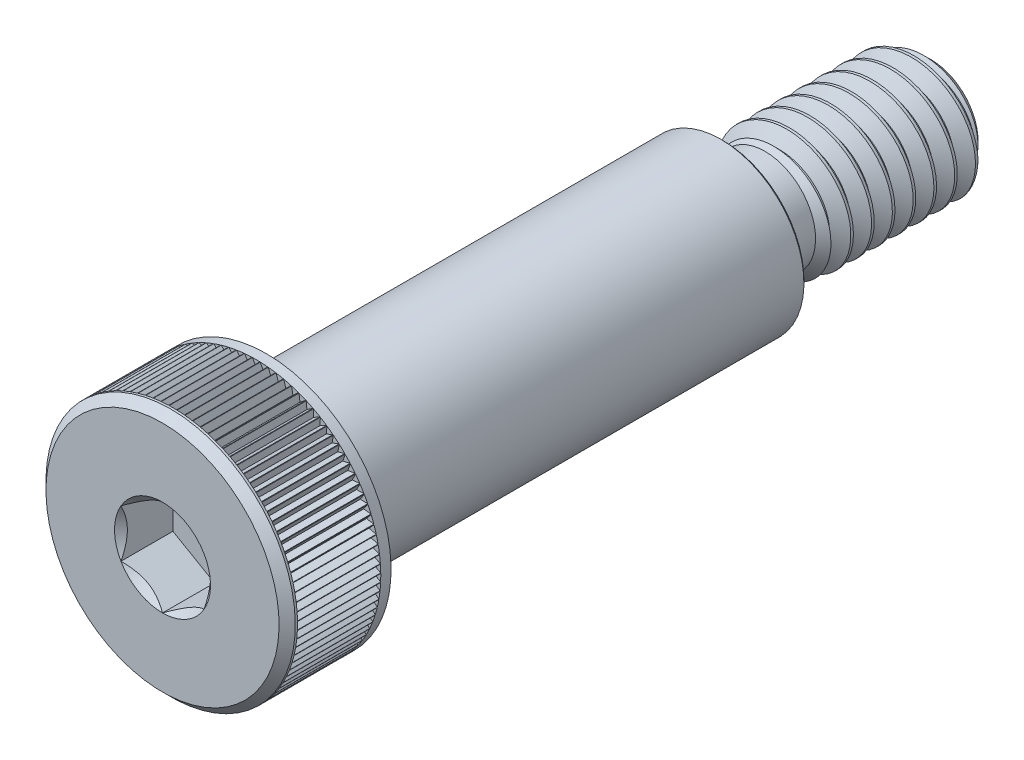
SolidWorks part; units mm, degrees
ref_plane "Front" through (0, 0, 0) normal (0, 0, 1) x (1, 0, 0)
ref_plane "Top" through (0, 0, 0) normal (0, 1, 0) x (1, 0, 0)
ref_plane "Right" through (0, 0, 0) normal (1, 0, 0) x (0, 0, -1)
sketch "Sketch1" plane through (0, 0, 0) normal (1, 0, 0) x (0, 0, -1)
  line L0 (0, 9.525) -> (7.9375, 9.525)
  line L1 (7.9375, 9.525) -> (7.9375, 6.35)
  line L2 (7.9375, 6.35) -> (42.8625, 6.35)
  line L3 (42.8625, 6.35) -> (42.8625, 4.7625)
  line L4 (42.8625, 4.7625) -> (58.7375, 4.7625)
  line L5 (58.7375, 4.7625) -> (58.7375, 0)
  line L6 (58.7375, 0) -> (0, 0)
  line L7 (0, 0) -> (0, 9.525)
  line L8 (0, 9.525) -> (0, -9.525) construction
  line L9 (58.7375, 4.7625) -> (58.7375, -4.7625) construction
  line L10 (42.8625, 6.35) -> (42.8625, -6.35) construction
  line L11 (58.7375, -4.7625) -> (57.0597, -4.7625) construction
  line L12 (25.4, 0) -> (25.4, 6.35) construction
  point P8 (56.3562, -4.7625)
  point P12 (42.8625, 0)
  point P17 (11.43, 6.35)
  point P18 (25.4, 0)
  point P19 (25.4, 6.35)
  point P20 (39.37, 6.35)
  point P21 (39.37, -6.35)
  point P22 (11.43, -6.35)
  dimension "D3" = 17.4625
  dimension "Head Dia" = 19.05
  dimension "Head Ht" = 7.9375
  dimension "Thread Lg" = 15.875
  dimension "Thread Dia" = 9.525
  dimension "Shoulder Dia" = 12.7
  dimension "Shoulder Lg" = 34.925
  dimension "D1" = 2.3813
  dimension "D2" = 1.6778
  dimension "D4" = 3.4925
revolve "Revolve1" add sketch "Sketch1" angle 360 mid plane about L6
ref_plane "Plane1" through (0, 0, -58.7375) normal (0, 0, 1) x (1, 0, 0)
sketch "Sketch3" plane through (0, 0, -58.7375) normal (0, 0, 1) x (1, 0, 0)
  circle A0 centre (0, 0) radius 4.7625
sketch "Sketch5" plane through (0, 0, 0) normal (1, 0, 0) x (0, 0, -1)
  line L0 (42.8625, 6.35) -> (48.5267, 6.35)
  line L1 (48.5267, 6.35) -> (46.0375, 3.8608)
  line L2 (46.0375, 3.8608) -> (43.7642, 3.8608)
  line L3 (42.8625, 6.35) -> (42.8625, 4.7625)
  line L5 (42.8625, 4.7625) -> (58.7375, 4.7625) construction
  line L6 (58.7375, 0) -> (46.0375, 0) construction
  line L7 (52.3875, 0) -> (52.3875, -4.7625) construction
  arc A0 (42.8625, 4.7625) -> (43.7642, 3.8608) centre (43.7642, 4.7625) ccw
  dimension "D1" = 45
  dimension "CADB" = 3.175
  dimension "CADA" = 7.7216
revolve "Cut-Revolve1" cut sketch "Sketch5" angle 360 mid plane about L6
chamfer "Chamfer1" distance 1.1906 angle 45 1 edges at (0, 4.7625, -58.7375)
chamfer "Chamfer2" distance 0.6191 angle 45 1 edges at (0, 9.525, 0)
chamfer "Chamfer3" distance 0.2032 angle 45 1 edges at (0, 6.35, -42.8625)
sketch "Sketch10" plane through (0, 0, 0) normal (1, 0, 0) x (0, 0, -1)
  line L0 (0.6191, 0) -> (7.3184, 0) construction
  line L1 (0.6191, -9.525) -> (0.6191, 9.525) construction
  line L3 (0.6191, 0) -> (0, 0) construction
  line L4 (7.3184, 0) -> (7.9375, 0) construction
  line L5 (7.9375, -9.525) -> (7.9375, 9.525) construction
  point P6 (3.9687, 0)
  dimension "D1" = 6.6992
ref_plane "Plane2" through (0, 0, -3.9687) normal (0, 0, 1) x (1, 0, 0)
sketch "Sketch11" plane through (0, 0, -3.9687) normal (0, 0, 1) x (1, 0, 0)
  line L0 (0, 9.0297) -> (0, 9.525) construction
  line L1 (0, 9.0297) -> (0.286, 9.525)
  line L2 (0, 9.0297) -> (-0.286, 9.525)
  line L3 (-0.286, 9.525) -> (0.286, 9.525)
  line L4 (0, 0) -> (-0.286, 9.525) construction
  line L5 (0.286, 9.525) -> (0, 0) construction
  circle A1 centre (0, 0) radius 9.525 construction
  circle A2 centre (0, 0) radius 9.0297 construction
  circle A3 centre (0, 0) radius 8.9059 construction
  point P3 (0, 0.0018)
  point P8 (2.3908, 0.7309)
  dimension "D1" = 0.4953
  dimension "D2" = 3.439
extrude "Cut-Extrude5" cut sketch "Sketch11" against normal mid plane 6.3643
pattern_circular "CirPattern1" count 99 over 360 about axis through (0, 0, -58.7375) along (0, 0, -1) of "Cut-Extrude5"
sketch "Sketch8" plane through (0, 0, 0) normal (0, 0, 1) x (1, 0, 0)
  line L1 (3.175, 1.8331) -> (0, 3.6662)
  line L2 (0, 3.6662) -> (-3.175, 1.8331)
  line L3 (-3.175, 1.8331) -> (-3.175, -1.8331)
  line L4 (-3.175, -1.8331) -> (0, -3.6662)
  line L5 (0, -3.6662) -> (3.175, -1.8331)
  line L6 (3.175, -1.8331) -> (3.175, 1.8331)
  circle A0 centre (0, 0) radius 3.175 construction
  dimension "Hex" = 6.35
extrude "Cut-Extrude2" cut sketch "Sketch8" against normal blind 3.9688
sketch "Sketch9" plane through (0, 0, 0) normal (0, 0, 1) x (1, 0, 0)
  circle A0 centre (0, 0) radius 3.6662
extrude "Cut-Extrude4" cut sketch "Sketch9" against normal blind 3.9688 draft 45
sketch "Front Sketch" plane through (0, 0, 0) normal (0, 0, 1) x (1, 0, 0)
  line L0 (3.175, -1.8331) -> (3.175, 1.8331) construction
  line L1 (-3.175, 1.8331) -> (-3.175, -1.8331) construction
  circle A0 centre (0, 0) radius 9.525 construction
  point P4 (-3.175, 0)
  point P5 (3.175, 0)
  point P6 (9.525, 0)
  point P9 (-9.525, 0)
ref_plane "Contact Plane 1" through (0, 0, -7.9375) normal (0, 0, -1) x (-1, 0, 0)
ref_axis "Center Axis 1" through (0, 0, -58.7375) along (0, 0, 1)
curve "Helix/Spiral1" pitch 1.5875 height 17.4625 radius 4.7625 centre (0, 0, -58.7375) axis (0, 0, 1) start towards (0, 1, 0)
sketch "Sketch4" plane through (0, 0, 0) normal (1, 0, 0) x (0, 0, -1)
  line L0 (58.6383, 4.9344) -> (60.2258, 4.9344) construction
  line L1 (60.2258, 4.9344) -> (59.432, 3.5595) construction
  line L3 (59.432, 3.5595) -> (58.6383, 4.9344) construction
  line L4 (58.6879, 4.8484) -> (60.1762, 4.8484) construction
  line L5 (58.7375, 4.7625) -> (60.1266, 4.7625) construction
  line L6 (59.3328, 3.7314) -> (59.5312, 3.7314) construction
  line L7 (59.432, 3.7314) -> (59.432, 3.5595) construction
  line L8 (59.432, 4.9344) -> (59.432, 4.7625) construction
  line L9 (58.6879, 4.8484) -> (60.1762, 4.8484)
  line L10 (60.1762, 4.8484) -> (59.5312, 3.7314)
  line L11 (59.5312, 3.7314) -> (59.3328, 3.7314)
  line L12 (59.3328, 3.7314) -> (58.6879, 4.8484)
  point P14 (59.432, 4.8484)
  point P15 (59.432, 4.9344)
  dimension "D1" = 1.5875
  dimension "D2" = 0.1984
sweep "Cut-Sweep1" cut profiles "Sketch4" path "Helix/Spiral1" align with end faces yes
sketch "Sketch12" plane through (0, 0, 0) normal (1, 0, 0) x (0, 0, -1)
  line L1 (42.8625, 6.1468) -> (42.6593, 6.35)
  line L2 (42.6593, 6.35) -> (7.9375, 6.35)
  line L3 (7.9375, 6.35) -> (7.9375, 0)
  line L4 (7.9375, -9.525) -> (7.9375, 9.525) construction
  line L5 (7.9375, 0) -> (42.8625, 0)
  line L6 (42.8625, 6.1468) -> (42.8625, 4.7625)
  line L7 (46.0375, 3.8608) -> (43.7642, 3.8608) construction
  line L8 (46.0375, 3.8608) -> (43.7642, 3.8608)
  line L9 (46.0375, 3.8608) -> (46.0375, 0)
  line L10 (46.0375, 0) -> (42.8625, 0)
  arc A0 (42.8625, 4.7625) -> (43.7642, 3.8608) centre (43.7642, 4.7625) ccw construction
  arc A1 (42.8625, 4.7625) -> (43.7642, 3.8608) centre (43.7642, 4.7625) ccw
revolve "Revolve2" add sketch "Sketch12" angle 360 about L5
equation "\"D3@Helix/Spiral1\" = \"Thread Lg@Sketch1\" + \"D4@Helix/Spiral1\""
equation "\"D1@Chamfer1\" = \"Thread Dia@Sketch1\" * .125"
equation "\"D1@Cut-Extrude2\"= \"Head Ht@Sketch1\" * .5"
equation "\"D1@Cut-Extrude4\" = \"D1@Cut-Extrude2\""
equation "\"D1@Chamfer2\" = \"Head Dia@Sketch1\" * .0325"
equation "\"D1@Sketch1\"=\"D4@Helix/Spiral1\"*1.5"
equation "\"D1@Sketch11\"=\"D1@Chamfer2\"*.8"
equation "\"D1@Cut-Extrude5\"=\"D1@Sketch10\"*.95"
equation "\"D1@CirPattern1\"=(360/\"D2@Sketch11\")-6"
equation "\"D3@Sketch1\"=\"Shoulder Lg@Sketch1\"/2"
equation "\"D4@Sketch1\"=\"D3@Sketch1\"*.2"
equation "\"D1@Sketch4\"=\"D4@Helix/Spiral1\""
equation "\"D2@Sketch4\"=\"D1@Sketch4\"/8"
